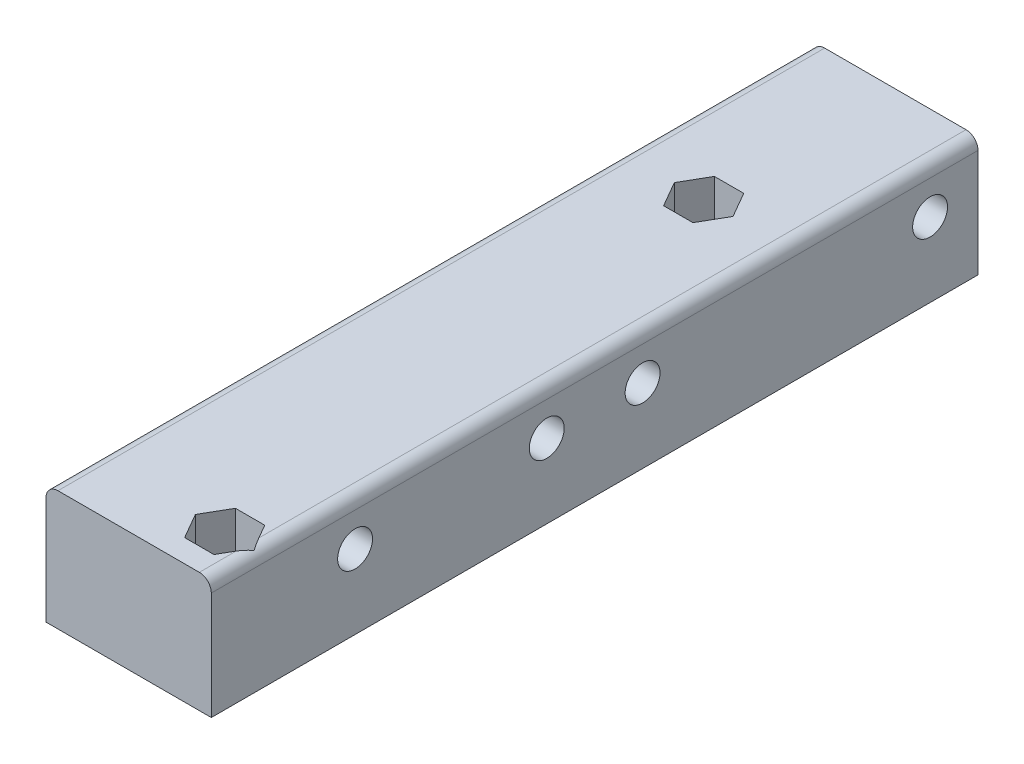
SolidWorks part; units mm, degrees
ref_plane "Front Plane" through (0, 0, 0) normal (0, 0, 1) x (1, 0, 0)
ref_plane "Top Plane" through (0, 0, 0) normal (0, 1, 0) x (1, 0, 0)
ref_plane "Right Plane" through (0, 0, 0) normal (1, 0, 0) x (0, 0, -1)
sketch "Sketch1" plane through (0, 0, 0) normal (0, 0, 1) x (1, 0, 0)
  line L1 (0, 0) -> (21.9075, 0)
  line L2 (0, 0) -> (0, 15.875)
  line L3 (0, 15.875) -> (21.9075, 15.875)
  line L4 (21.9075, 0) -> (21.9075, 15.875)
  dimension "D1" = 21.9075
  dimension "D2" = 15.875
extrude "Boss-Extrude1" add sketch "Sketch1" along normal blind 101.6
fillet "Fillet1" radius 1.5875 2 edges at (21.9075, 15.875, 50.8) (0, 15.875, 50.8)
sketch "Sketch2" plane through (21.9075, 0, 0) normal (1, 0, 0) x (0, 0, -1)
  circle A0 centre (-57.15, 9.8298) radius 2.3114 construction
  circle A1 centre (-57.15, 9.8298) radius 2.3114
  circle A2 centre (-44.45, 9.8298) radius 2.3114 construction
  circle A3 centre (-44.45, 9.8298) radius 2.3114
  circle A4 centre (-82.55, 9.8298) radius 2.3114 construction
  circle A5 centre (-82.55, 9.8298) radius 2.3114
  circle A6 centre (-6.35, 9.8298) radius 2.3114 construction
  circle A7 centre (-6.35, 9.8298) radius 2.3114
extrude "Cut-Extrude2" cut sketch "Sketch2" against normal up to surface (21.9075 mm away) up to face at (0, 7.1437, 50.8)
sketch "Sketch3" plane through (0, 0, 0) normal (0, -1, 0) x (1, 0, 0)
  line L0 (0, 101.6) -> (21.9075, 101.6) construction
  line L1 (19.2468, 98.5888) -> (15.3607, 98.5888)
  line L2 (15.3607, 98.5888) -> (13.4176, 95.2233)
  line L3 (13.4176, 95.2233) -> (15.3607, 91.8578)
  line L4 (15.3607, 91.8578) -> (19.2468, 91.8578)
  line L5 (19.2468, 91.8578) -> (21.1899, 95.2233)
  line L6 (21.1899, 95.2233) -> (19.2468, 98.5888)
  line L7 (12.8968, 28.7655) -> (9.0107, 28.7655)
  line L8 (9.0107, 28.7655) -> (7.0676, 25.4)
  line L9 (7.0676, 25.4) -> (9.0107, 22.0345)
  line L10 (9.0107, 22.0345) -> (12.8968, 22.0345)
  line L11 (12.8968, 22.0345) -> (14.8399, 25.4)
  line L12 (14.8399, 25.4) -> (12.8968, 28.7655)
  line L13 (21.9075, 101.6) -> (21.9075, 0) construction
  line L14 (0, 101.6) -> (0, 0) construction
  line L15 (0, 0) -> (21.9075, 0) construction
  circle A4 centre (17.3037, 95.2233) radius 3.3655 construction
  circle A5 centre (10.9537, 25.4) radius 3.3655 construction
  point P1 (0, 0)
  dimension "D1" = 6.731
  dimension "D2" = 6.731
  dimension "D3" = 6.3767
  dimension "D4" = 4.6038
  dimension "D5" = 10.9537
  dimension "D6" = 25.4
extrude "Cut-Extrude3" cut sketch "Sketch3" against normal up to next
